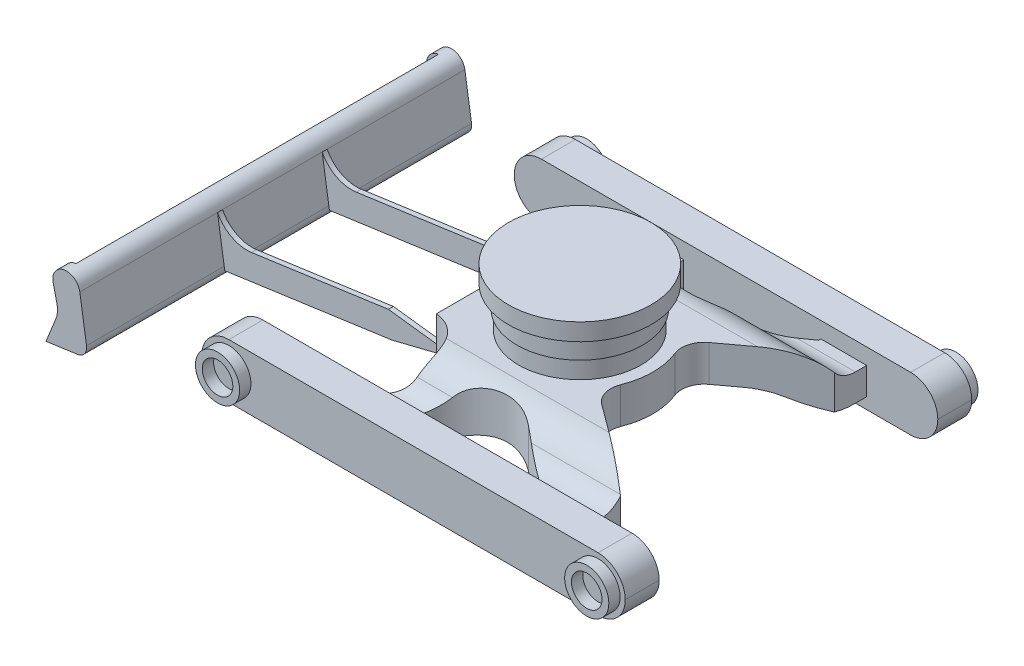
SolidWorks part; units mm, degrees
material "Stainless Steel (ferritic)"
ref_plane "Plano frontal" through (0, 0, 0) normal (0, 0, 1) x (1, 0, 0)
ref_plane "Plano superior" through (0, 0, 0) normal (0, 1, 0) x (1, 0, 0)
ref_plane "Plano direito" through (0, 0, 0) normal (1, 0, 0) x (0, 0, -1)
sketch "Sketch1" plane through (0, 0, 0) normal (0, 1, 0) x (1, 0, 0)
  line L0 (1556, 0) -> (1556, 143)
  line L1 (0, 0) -> (1870, 0) construction
  line L2 (0, 0) -> (0, -195.2002) construction
  line L3 (0, -195.2002) -> (1870, -195.2002) construction
  line L4 (1870, 0) -> (1870, -195.2002) construction
  line L5 (1556, 0) -> (1354, 0)
  line L6 (1354, 0) -> (1354, 10)
  line L8 (1354, 10) -> (1115.4468, 176.5412)
  line L9 (748, 0) -> (490, 0)
  line L10 (1556, 143) -> (1237.9786, 378.3234)
  line L11 (0, 1230) -> (1870, 1230) construction
  line L12 (0, 615) -> (2690.0624, 615) construction
  line L13 (526.3933, 870) -> (526.3933, 360)
  line L14 (1556, 1087) -> (1237.9786, 851.6766)
  line L15 (1556, 1230) -> (1556, 1087)
  line L16 (1556, 1230) -> (1354, 1230)
  line L17 (748, 1230) -> (490, 1230)
  line L18 (1354, 1220) -> (1115.4468, 1053.4588)
  line L20 (1354, 1230) -> (1354, 1220)
  line L21 (490, 0) -> (490, 10)
  line L22 (490, 1230) -> (490, 1220)
  arc A0 (1115.4468, 176.5412) -> (748, 0) centre (981.4975, -15.3274) ccw
  arc A2 (1204.5371, 495.6573) -> (1204.5371, 734.3427) centre (904.3933, 615) ccw
  arc A3 (1115.4468, 1053.4588) -> (748, 1230) centre (981.4975, 1245.3274) cw
  arc A4 (490, 10) -> (665.5209, 206.7198) centre (467.5209, 206.7198) ccw
  arc A5 (665.5209, 206.7198) -> (526.3933, 360) centre (511.5209, 206.7198) ccw
  arc A6 (665.5209, 1023.2802) -> (526.3933, 870) centre (511.5209, 1023.2802) cw
  arc A7 (490, 1220) -> (665.5209, 1023.2802) centre (467.5209, 1023.2802) cw
  arc A8 (1237.9786, 378.3234) -> (1204.5371, 495.6573) centre (1297.4609, 458.7091) cw
  arc A9 (1237.9786, 851.6766) -> (1204.5371, 734.3427) centre (1297.4609, 771.2909) ccw
  point P23 (526.3933, 615)
  point P44 (1168.8157, 429.5013)
  point P47 (1168.8157, 800.4987)
  dimension "D2" = 314
  dimension "D8" = 234
  dimension "D15" = 646
  dimension "D6" = 198
  dimension "D7" = 154
  dimension "D18" = 100
  dimension "D1" = 1870
  dimension "D3" = 143
  dimension "D4" = 202
  dimension "D5" = 10
  dimension "D9" = 258
  dimension "D10" = 1230
  dimension "D11" = 615
  dimension "D12" = 526.3933
  dimension "D13" = 904.3933
  dimension "D16" = 73
  dimension "D17" = 10
  dimension "D19" = 510
  dimension "D20" = 490
extrude "Boss-Extrude1" add sketch "Sketch1" along normal mid plane 250 contours L14 A9 A2 A8 L10 L0 L5 L6 L8 A0 L9 L21 A4 A5 L13 A6 A7 L22 L17 A3 L18 L20 L16 L15
sketch "Sketch2" plane through (0, 0, 0) normal (1, 0, 0) x (0, 0, -1)
  line L0 (615, 290.8561) -> (615, -240.4917) construction
  line L1 (287.3065, 125) -> (942.6935, 125)
  line L2 (143, 125) -> (378.3234, 125) construction
  line L3 (1087, 125) -> (851.6766, 125) construction
  line L4 (1230, 7.2487) -> (1230, -112.7513)
  line L5 (1180, 7.2487) -> (1230, 7.2487)
  line L6 (0, -112.7513) -> (50, -112.7513)
  line L7 (50, 7.2487) -> (0, 7.2487)
  line L8 (0, 7.2487) -> (0, -112.7513)
  line L10 (312.7974, -35) -> (917.2026, -35)
  line L11 (1230, 125) -> (1230, -125) construction
  line L12 (1230, -112.7513) -> (1180, -112.7513)
  arc A0 (942.6935, 125) -> (1084.4403, 54.6654) centre (942.6935, -53) cw
  arc A1 (1084.4403, 54.6654) -> (1180, 7.2487) centre (1180, 127.2487) ccw
  arc A2 (917.2026, -35) -> (993.9199, -57.6976) centre (917.2026, -176) cw
  arc A3 (1180, -112.7513) -> (993.9199, -57.6976) centre (1180, 229.2487) cw
  arc A4 (50, -112.7513) -> (236.0801, -57.6976) centre (50, 229.2487) ccw
  arc A5 (312.7974, -35) -> (236.0801, -57.6976) centre (312.7974, -176) ccw
  arc A6 (145.5597, 54.6654) -> (50, 7.2487) centre (50, 127.2487) cw
  arc A7 (287.3065, 125) -> (145.5597, 54.6654) centre (287.3065, -53) ccw
  dimension "D2" = 178
  dimension "D3" = 120
  dimension "D5" = 342
  dimension "D6" = 141
  dimension "D1" = 160
  dimension "D4" = 120
  dimension "D7" = 50
extrude "Cut-Extrude1" cut sketch "Sketch2" against normal through all both and the other way through all flip side to cut contours L5 L4 L12 A3 A2 L10 A5 A4 L6 L8 L7 A6 A7 L1 A0 A1
ref_plane "Plane1" through (0, 0, -615) normal (0, 0, 1) x (1, 0, 0)
sketch "Sketch4" plane through (0, 0, -615) normal (0, 0, 1) x (1, 0, 0)
  line L0 (904.3933, 125) -> (904.3933, 549.8962) construction
  line L3 (634.3933, 125) -> (634.3933, 205)
  line L4 (634.3933, 205) -> (626.8933, 205)
  line L5 (626.8933, 205) -> (626.8933, 285)
  line L6 (626.8933, 285) -> (634.3933, 285)
  line L7 (589.3933, 302) -> (589.3933, 378)
  line L8 (589.3933, 378) -> (904.3933, 378)
  line L9 (904.3933, 378) -> (904.3933, 125)
  line L10 (904.3933, 125) -> (634.3933, 125)
  line L11 (634.3933, 285) -> (634.3933, 302)
  line L12 (634.3933, 302) -> (589.3933, 302)
  dimension "D2" = 80
  dimension "D3" = 630
  dimension "D4" = 555
  dimension "D5" = 540
  dimension "D6" = 80
  dimension "D7" = 76
  dimension "D8" = 17
  dimension "D9" = 540
revolve "Revolve2" add sketch "Sketch4" angle 360 about L0
sketch "Sketch5" plane through (0, 0, 0) normal (0, 1, 0) x (1, 0, 0)
  line L1 (0, 0) -> (1870, 0)
  line L2 (0, 0) -> (0, -150)
  line L3 (0, -150) -> (1870, -150)
  line L4 (1870, 0) -> (1870, -150)
  dimension "D2" = 150
  dimension "D1" = 1870
extrude "Boss-Extrude2" add sketch "Sketch5" along normal blind 240 from offset 162 contours L2 L3 L4 L1 offset against normal yes
sketch "Sketch6" plane through (0, 0, 150) normal (0, 0, 1) x (1, 0, 0)
  line L0 (0, 78) -> (0, -162) construction
  line L1 (0, 78) -> (1870, 78) construction
  circle A0 centre (120, -42) radius 97.5
  circle A1 centre (1750, -42) radius 97.5
  circle A2 centre (120, -42) radius 67.5
  circle A3 centre (1750, -42) radius 67.5
  dimension "D1" = 195
  dimension "D2" = 135
  dimension "D3" = 1630
  dimension "D4" = 120
  dimension "D5" = 120
extrude "Boss-Extrude3" add sketch "Sketch6" along normal blind 50
mirror "Mirror1" about plane through (0, 0, -615) normal (0, 0, 1) of bodies 106
ref_plane "Plane2" through (0, 0, -615) normal (0, 0, 1) x (1, 0, 0)
sketch "Sketch7" plane through (0, 0, -615) normal (0, 0, 1) x (1, 0, 0)
  line L0 (526.3933, -35) -> (316.7391, -86.9723)
  line L1 (526.3933, 125) -> (526.3933, -35) construction
  line L2 (316.7391, -86.9723) -> (-421.0106, -190.6562)
  line L3 (642.7527, 125) -> (526.3933, 125) construction
  line L4 (301.2909, 22.9475) -> (-302.825, -61.9555)
  line L5 (0, 78) -> (1870, 78) construction
  line L6 (301.2909, 22.9475) -> (526.3933, -5)
  line L7 (526.3933, -5) -> (526.3933, -35)
  line L8 (-453.0218, 15.9315) -> (-421.0106, -190.6562)
  arc A0 (-302.825, -61.9555) -> (-453.0218, 15.9315) centre (-323.1443, 82.6237) cw
  dimension "D5" = 146
  dimension "D1" = 160
  dimension "D2" = 216
  dimension "D3" = 745
  dimension "D6" = 130
  dimension "D7" = 21
  dimension "D4" = 111
  dimension "D8" = 8
extrude "Boss-Extrude4" add sketch "Sketch7" against normal blind 22 from offset 242
mirror "Mirror2" about plane through (0, 0, -615) normal (0, 0, 1) of "Boss-Extrude4"
sketch "Sketch8" plane through (0, 0, -615) normal (0, 0, 1) x (1, 0, 0)
  line L0 (-453.0218, 15.9315) -> (-423.4752, -174.7507)
  line L1 (-570.7764, -6.753) -> (-554.0243, -79.3145)
  line L2 (-602.3734, -247.2594) -> (-462.7456, -227.636)
  line L3 (-421.0106, -190.6562) -> (316.7391, -86.9723) construction
  line L4 (-453.0218, 15.9315) -> (-421.0106, -190.6562) construction
  line L5 (-558.7429, -139.2702) -> (-602.3734, -247.2594)
  arc A0 (-453.0218, 15.9315) -> (-570.7764, -6.753) centre (-512.3142, 6.7441) ccw
  arc A1 (-462.7456, -227.636) -> (-423.4752, -174.7507) centre (-469.1827, -181.8332) ccw
  arc A2 (-554.0243, -79.3145) -> (-558.7429, -139.2702) centre (-651.4613, -101.8096) cw
  point P12 (-546.9316, -110.0362)
  dimension "D1" = 95
  dimension "D2" = 106
  dimension "D3" = 148
  dimension "D4" = 35
  dimension "D6" = 60
  dimension "D7" = 100
  dimension "D5" = 141
extrude "Boss-Extrude5" add sketch "Sketch8" along normal mid plane 1700 contours L0 A1 L2 L5 A2 L1 A0
sketch "Sketch9" plane through (0, 0, -615) normal (0, 0, 1) x (1, 0, 0)
  line L0 (-593.2896, -224.7764) -> (-471.4867, -207.6581)
  line L1 (-602.3734, -247.2594) -> (-462.7456, -227.636) construction
  line L2 (-471.4867, -207.6581) -> (-519.7888, 66.2767)
  line L5 (-570.7764, -6.753) -> (-554.0243, -79.3145) construction
  line L6 (-558.7429, -139.2702) -> (-602.3734, -247.2594) construction
  line L8 (-570.7764, -6.753) -> (-554.0243, -79.3145)
  line L9 (-558.7429, -139.2702) -> (-593.2896, -224.7764)
  arc A2 (-453.0218, 15.9315) -> (-570.7764, -6.753) centre (-512.3142, 6.7441) ccw construction
  arc A3 (-519.7888, 66.2767) -> (-570.7764, -6.753) centre (-512.3142, 6.7441) ccw
  arc A4 (-558.7429, -139.2702) -> (-554.0243, -79.3145) centre (-651.4613, -101.8096) ccw construction
  arc A5 (-558.7429, -139.2702) -> (-554.0243, -79.3145) centre (-651.4613, -101.8096) ccw
  dimension "D1" = 21
  dimension "D2" = 3
  dimension "D3" = 123
extrude "Cut-Extrude2" cut sketch "Sketch9" against normal mid plane 1600
fillet "Fillet1" radius 120 8 edges at (1870, -162, -1305) (1870, 78, -1305) (0, -162, -1305) (0, 78, -1305) (0, -162, 75) (0, 78, 75) (1870, -162, 75) (1870, 78, 75)
